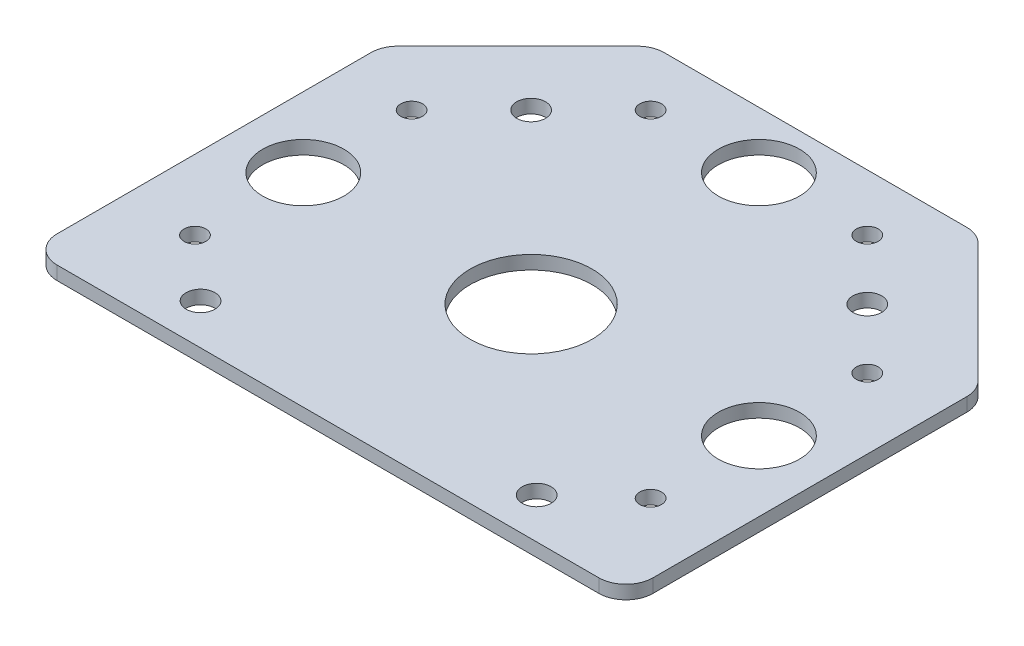
SolidWorks part; units mm, degrees
material "6061 Alloy"
ref_plane "Front Plane" through (0, 0, 0) normal (0, 0, 1) x (1, 0, 0)
ref_plane "Top Plane" through (0, 0, 0) normal (0, 1, 0) x (1, 0, 0)
ref_plane "Right Plane" through (0, 0, 0) normal (1, 0, 0) x (0, 0, -1)
sketch "Sketch1" plane through (0, 0, 0) normal (0, 1, 0) x (1, 0, 0)
  line L7 (-69.85, -57.15) -> (69.85, -57.15)
  line L8 (-69.85, -57.15) -> (-69.85, 57.15)
  line L9 (-69.85, 57.15) -> (69.85, 57.15)
  line L10 (69.85, -57.15) -> (69.85, 57.15)
  line L11 (-69.85, -57.15) -> (69.85, 57.15) construction
  line L12 (-69.85, 57.15) -> (69.85, -57.15) construction
  circle A2 centre (0, 43.8912) radius 9.525
  circle A3 centre (-53.4162, -9.525) radius 9.525
  circle A4 centre (53.4162, -9.525) radius 9.525
  circle A5 centre (0, -9.525) radius 14.2875
  circle A6 centre (0, -9.525) radius 53.4162 construction
  point P0 (0, 0)
  dimension "D3" = 28.575
  dimension "D4" = 9.525
  dimension "D5" = 19.05
  dimension "D6" = 19.05
  dimension "D7" = 19.05
  dimension "D8" = 106.8324
  dimension "D1" = 139.7
  dimension "D2" = 114.3
extrude "Boss-Extrude1" add sketch "Sketch1" along normal mid plane 3.175
hole_wizard "#10 Clearance Hole1" positions "Sketch3" profile "Sketch4" hole size "#10" standard "ANSI Inch" end condition up to next
sketch "Sketch3" plane through (0, 1.5875, 0) normal (0, 1, 0) x (1, 0, 0)
  circle A0 centre (53.4162, -9.525) radius 9.525 construction
  circle A1 centre (0, 43.8912) radius 9.525 construction
  circle A2 centre (-53.4162, -9.525) radius 9.525 construction
  circle A3 centre (53.4162, -9.525) radius 9.525
  circle A4 centre (0, 43.8912) radius 9.525
  circle A5 centre (-53.4162, -9.525) radius 9.525
  circle A6 centre (-53.4162, -9.525) radius 25.4 construction
  circle A7 centre (0, 43.8912) radius 25.4 construction
  circle A8 centre (53.4162, -9.525) radius 25.4 construction
  point P0 (-53.4162, 15.875)
  point P16 (-53.4162, -34.925)
  point P22 (-25.4, 43.8912)
  point P24 (25.4, 43.8912)
  point P29 (53.4162, 15.875)
  point P31 (53.4162, -34.925)
  dimension "D1" = 50.8
  dimension "D2" = 50.8
  dimension "D3" = 50.8
sketch "Sketch4" plane through (-53.4162, 1.5875, -15.875) normal (1, 0, 0) x (0, 0, 1)
  line L0 (0, 0) -> (0, 3.175)
  line L1 (0, 3.175) -> (2.5527, 3.175)
  line L2 (2.5527, 3.175) -> (2.5527, 0)
  line L5 (2.5527, 0) -> (0, 0)
  line L11 (0, -6.35) -> (0, 107.95) construction
  dimension "Thru Hole Dia." = 5.1054
  dimension "Thru Hole Depth" = 3.175
hole_wizard "1/4 Clearance Hole1" positions "Sketch5" profile "Sketch6" hole size "1/4" standard "ANSI Inch" end condition up to next
sketch "Sketch5" plane through (0, 1.5875, 0) normal (0, 1, 0) x (1, 0, 0)
  line L0 (25.4, 43.8912) -> (53.4162, 15.875) construction
  line L2 (-25.4, 43.8912) -> (-53.4162, 15.875) construction
  circle A0 centre (0, -9.525) radius 14.2875 construction
  circle A1 centre (0, -9.525) radius 14.2875
  circle A2 centre (-53.4162, 15.875) radius 2.5527 construction
  circle A3 centre (-25.4, 43.8912) radius 2.5527 construction
  circle A4 centre (25.4, 43.8912) radius 2.5527 construction
  circle A5 centre (53.4162, 15.875) radius 2.5527 construction
  circle A6 centre (-53.4162, 15.875) radius 2.5527
  circle A7 centre (-25.4, 43.8912) radius 2.5527
  circle A8 centre (25.4, 43.8912) radius 2.5527
  circle A9 centre (53.4162, 15.875) radius 2.5527
  point P0 (-39.4081, 29.8831)
  point P13 (39.4081, 29.8831)
  point P15 (-39.4081, -47.625)
  point P17 (39.4081, -47.625)
  point P38 (39.4081, 29.8831)
  point P39 (-39.4081, 29.8831)
  point P40 (0, 0)
  point P41 (0, 0)
  dimension "D3" = 38.1
sketch "Sketch6" plane through (-39.4081, 1.5875, -29.8831) normal (1, 0, 0) x (0, 0, 1)
  line L0 (0, 0) -> (0, 3.175)
  line L1 (0, 3.175) -> (3.3782, 3.175)
  line L2 (3.3782, 3.175) -> (3.3782, 0)
  line L5 (3.3782, 0) -> (0, 0)
  line L11 (0, -6.35) -> (0, 107.95) construction
  dimension "Thru Hole Dia." = 6.7564
  dimension "Thru Hole Depth" = 3.175
chamfer "Chamfer1" distance 31.75 angle 45 2 edges at (69.85, 0, -57.15) (-69.85, 0, -57.15)
fillet "Fillet2" radius 6.35 6 edges at (-69.85, 0, 57.15) (69.85, 0, 57.15) (69.85, 0, -25.4) (38.1, 0, -57.15) (-38.1, 0, -57.15) (-69.85, 0, -25.4)
